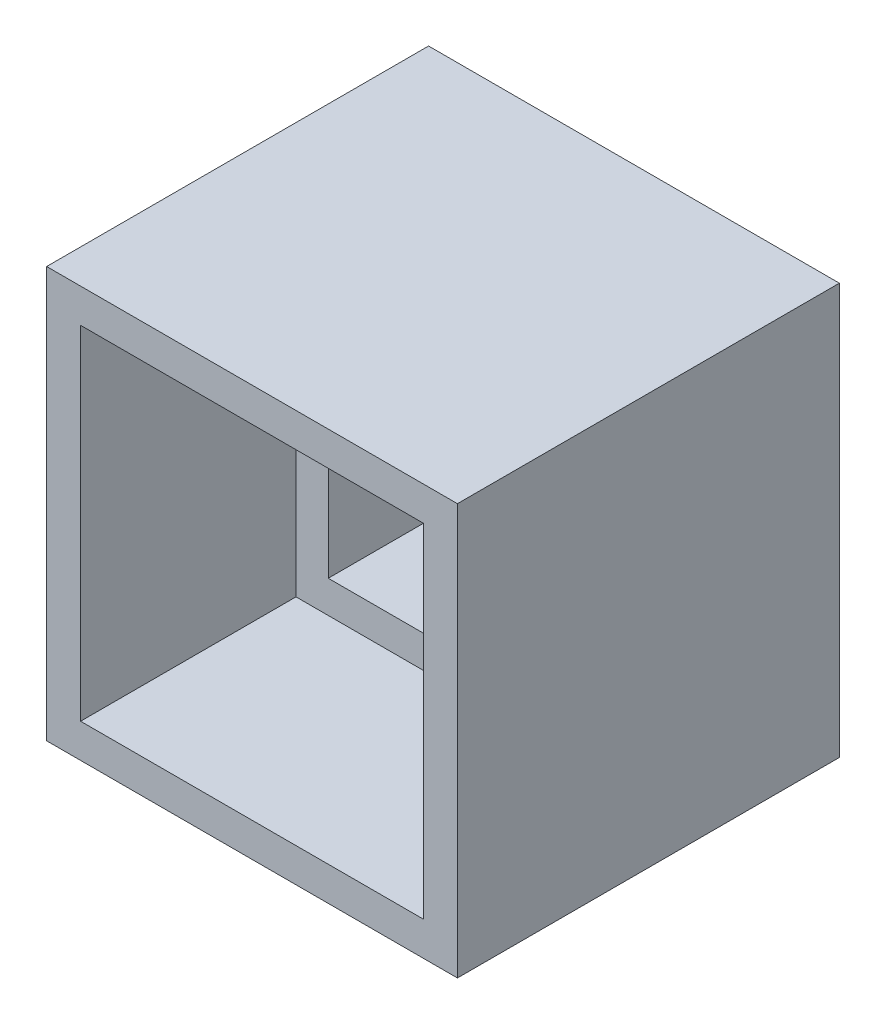
SolidWorks part; units mm, degrees
ref_plane "Front Plane" through (0, 0, 0) normal (0, 0, 1) x (1, 0, 0)
ref_plane "Top Plane" through (0, 0, 0) normal (0, 1, 0) x (1, 0, 0)
ref_plane "Right Plane" through (0, 0, 0) normal (1, 0, 0) x (0, 0, -1)
sketch "Sketch1" plane through (0, 0, 0) normal (0, 0, 1) x (1, 0, 0)
  line L0 (-30.734, 30.734) -> (30.734, 30.734)
  line L1 (-20.828, 20.828) -> (20.828, 20.828)
  line L2 (-20.828, 20.828) -> (-20.828, -20.828)
  line L3 (-20.828, -20.828) -> (20.828, -20.828)
  line L4 (20.828, 20.828) -> (20.828, -20.828)
  line L5 (-20.828, 20.828) -> (20.828, -20.828) construction
  line L6 (-20.828, -20.828) -> (20.828, 20.828) construction
  line L7 (30.734, 30.734) -> (30.734, -30.734)
  line L8 (-30.734, -30.734) -> (30.734, -30.734)
  line L9 (-30.734, 30.734) -> (-30.734, -30.734)
  point P0 (0, 0)
  dimension "D1" = 41.656
  dimension "D2" = 9.906
extrude "Boss-Extrude1" add sketch "Sketch1" along normal blind 50.8 and the other way blind 6.35 contours L0 L7 L8 L9
extrude "Cut-Extrude1" cut sketch "Sketch1<3>" along normal through all contours L1 L4 L3 L2
sketch "Sketch1<3>" plane through (0, 0, 0) normal (0, 0, 1) x (1, 0, 0) same geometry as "Sketch1"
sketch "Sketch3" plane through (0, 30.734, 0) normal (0, 1, 0) x (1, 0, 0)
  line L0 (-30.734, 6.35) -> (-30.734, -50.8) construction
  line L1 (30.734, 6.35) -> (30.734, -50.8) construction
  line L2 (-30.734, 6.35) -> (-30.734, 0) construction
  line L3 (-30.734, 0) -> (30.734, 0) construction
  point P0 (-30.734, 3.175)
  point P1 (30.734, 3.175)
  point P11 (-30.734, 3.175)
ref_plane "Plane1" through (0, 0, -3.175) normal (0, 0, 1) x (1, 0, 0)
ref_plane "Plane2" through (0, 0, 32.258) normal (0, 0, 1) x (1, 0, 0)
sketch "Sketch2" plane through (0, 0, 32.258) normal (0, 0, 1) x (1, 0, 0)
  line L0 (30.734, 30.734) -> (30.734, -30.734) construction
  line L1 (-25.654, 25.654) -> (25.654, 25.654)
  line L2 (-25.654, 25.654) -> (-25.654, -25.654)
  line L3 (-25.654, -25.654) -> (25.654, -25.654)
  line L4 (25.654, 25.654) -> (25.654, -25.654)
  line L5 (-25.654, 25.654) -> (25.654, -25.654) construction
  line L6 (-25.654, -25.654) -> (25.654, 25.654) construction
  point P0 (0, 0)
  dimension "D1" = 5.08
sketch "Sketch5" plane through (0, 0, -6.35) normal (0, 0, -1) x (-1, 0, 0)
  line L1 (-19.05, 19.05) -> (19.05, 19.05)
  line L2 (-19.05, 19.05) -> (-19.05, -19.05)
  line L3 (-19.05, -19.05) -> (19.05, -19.05)
  line L4 (19.05, 19.05) -> (19.05, -19.05)
  line L5 (-19.05, 19.05) -> (19.05, -19.05) construction
  line L6 (-19.05, -19.05) -> (19.05, 19.05) construction
  point P0 (0, 0)
  dimension "D1" = 38.1
extrude "Cut-Extrude3" cut sketch "Sketch5" against normal through all
ref_plane "Plane4" through (0, 0, 18.5674) normal (0, 0, -1) x (-1, 0, 0)
sketch "Sketch7" plane through (0, 0, 18.5674) normal (0, 0, -1) x (-1, 0, 0)
  line L4 (25.654, 25.654) -> (-25.654, 25.654)
  line L5 (-25.654, 25.654) -> (-25.654, -25.654)
  line L6 (-25.654, -25.654) -> (25.654, -25.654)
  line L7 (25.654, -25.654) -> (25.654, 25.654)
  line L8 (25.654, 25.654) -> (-25.654, 25.654)
  line L9 (-25.654, 25.654) -> (-25.654, -25.654)
  line L10 (-25.654, -25.654) -> (25.654, -25.654)
  line L11 (25.654, -25.654) -> (25.654, 25.654)
  dimension "D1" = 0
extrude "Cut-Extrude4" cut sketch "Sketch7" against normal through all
